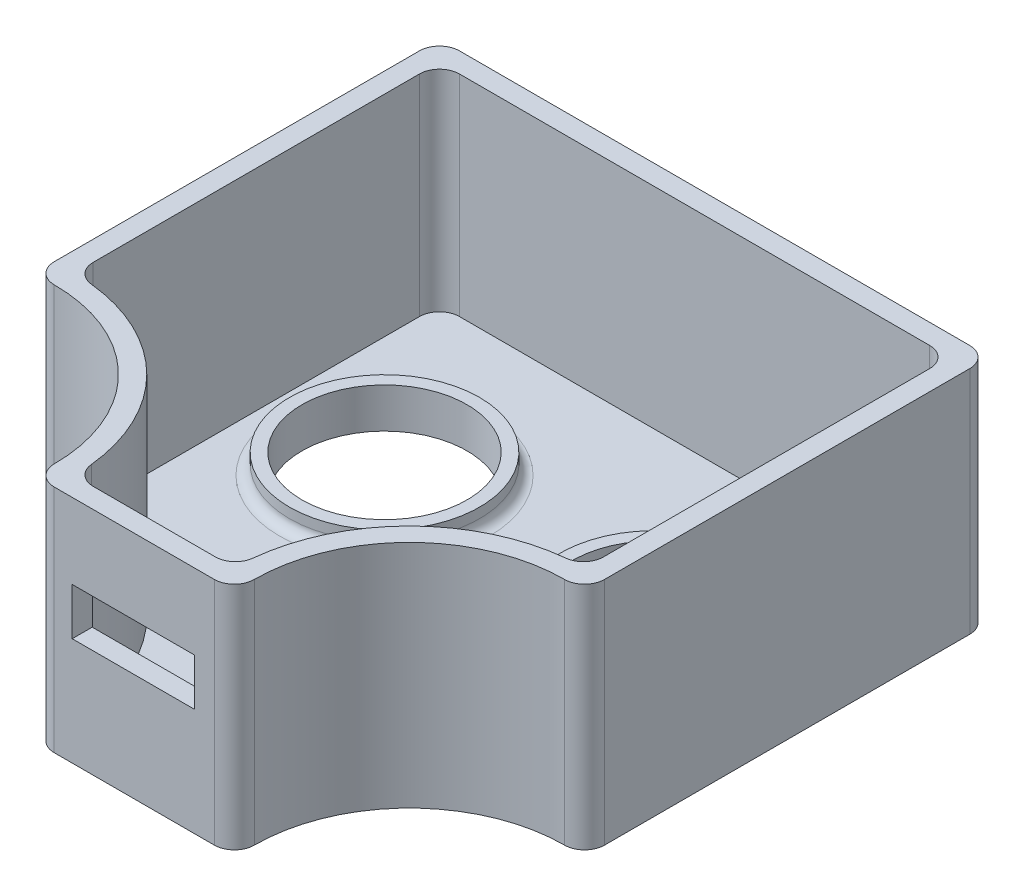
SolidWorks part; units mm, degrees
ref_plane "Alzado" through (0, 0, 0) normal (0, 0, 1) x (1, 0, 0)
ref_plane "Planta" through (0, 0, 0) normal (0, 1, 0) x (1, 0, 0)
ref_plane "Vista lateral" through (0, 0, 0) normal (1, 0, 0) x (0, 0, -1)
sketch "Croquis1" plane through (0, 0, 0) normal (0, 1, 0) x (1, 0, 0)
  line L0 (-13.8608, 0) -> (-3.3608, 0) construction
  line L1 (-8.6108, 17.491) -> (-8.6108, -38.509) construction
  line L2 (-8.7014, -42.647) -> (-14.8014, -42.647) construction
  line L3 (-32.1108, 17.491) -> (14.8892, 17.491)
  line L4 (-34.1108, 15.491) -> (-34.1108, -17.1118)
  line L5 (16.8892, -36.3999) -> (16.8892, -36.509)
  line L6 (16.8892, 15.491) -> (16.8892, -17.1118)
  line L7 (-34.1108, 17.491) -> (16.8892, -36.509) construction
  line L8 (-34.1108, -36.509) -> (16.8892, 17.491) construction
  line L9 (-34.1108, 19.491) -> (16.8892, 19.491)
  line L10 (-36.1108, 17.491) -> (-36.1108, -19.009)
  line L11 (-16.6108, -38.509) -> (-0.6108, -38.509)
  line L12 (18.8892, 17.491) -> (18.8892, -19.009)
  line L13 (-36.1108, 19.491) -> (18.8892, -38.509) construction
  line L14 (-36.1108, -38.509) -> (18.8892, 19.491) construction
  line L15 (-8.7014, -42.647) -> (-2.6014, -42.647)
  line L16 (-14.8014, -42.647) -> (-14.8014, -34.0287) construction
  line L17 (-14.8014, -34.0287) -> (-2.6014, -34.0287) construction
  line L18 (-2.6014, -34.0287) -> (-2.6014, -42.647) construction
  line L20 (-34.1108, -36.3999) -> (-34.1108, -36.509)
  line L21 (-14.7136, -36.509) -> (-2.5079, -36.509)
  circle A0 centre (-22.1108, 0) radius 8.25
  circle A1 centre (4.8892, 0) radius 8.25
  circle A2 centre (-22.1108, 0) radius 9.5
  circle A3 centre (4.8892, 0) radius 9.5
  arc A4 (-16.7031, -34.7141) -> (-32.3159, -19.1013) centre (-34.1108, -36.509) ccw
  arc A5 (-18.6108, -36.509) -> (-34.1108, -21.009) centre (-34.1108, -36.509) ccw
  arc A6 (15.0943, -19.1013) -> (-0.5185, -34.7141) centre (16.8892, -36.509) ccw
  arc A7 (16.8892, -21.009) -> (1.3892, -36.509) centre (16.8892, -36.509) ccw
  arc A8 (-32.3159, -19.1013) -> (-34.1108, -17.1118) centre (-32.1108, -17.1118) cw
  arc A9 (-36.1108, -19.009) -> (-34.1108, -21.009) centre (-34.1108, -19.009) ccw
  arc A10 (-16.7031, -34.7141) -> (-14.7136, -36.509) centre (-14.7136, -34.509) ccw
  arc A11 (-18.6108, -36.509) -> (-16.6108, -38.509) centre (-16.6108, -36.509) ccw
  arc A12 (1.3892, -36.509) -> (-0.6108, -38.509) centre (-0.6108, -36.509) cw
  arc A13 (-2.5079, -36.509) -> (-0.5185, -34.7141) centre (-2.5079, -34.509) ccw
  arc A14 (18.8892, -19.009) -> (16.8892, -21.009) centre (16.8892, -19.009) cw
  arc A15 (16.8892, -17.1118) -> (15.0943, -19.1013) centre (14.8892, -17.1118) cw
  arc A16 (18.8892, 17.491) -> (16.8892, 19.491) centre (16.8892, 17.491) ccw
  arc A17 (-34.1108, 19.491) -> (-36.1108, 17.491) centre (-34.1108, 17.491) ccw
  arc A18 (16.8892, 15.491) -> (14.8892, 17.491) centre (14.8892, 15.491) ccw
  arc A19 (-32.1108, 17.491) -> (-34.1108, 15.491) centre (-32.1108, 15.491) ccw
  point P6 (-8.6108, 0)
  point P9 (-8.6108, -9.509)
  point P16 (-8.6108, -9.509)
  dimension "D1" = 16.5
  dimension "D2" = 16.5
  dimension "D6" = 19
  dimension "D7" = 19
  dimension "D8" = 54
  dimension "D12" = 35
  dimension "D13" = 31
  dimension "D14" = 35
  dimension "D15" = 31
  dimension "D16" = 2
  dimension "D3" = 27
  dimension "D4" = 56
  dimension "D5" = 51
  dimension "D9" = 55
  dimension "D10" = 6.1
  dimension "D11" = 6.1
extrude "Saliente-Extruir1" add sketch "Croquis1" along normal blind 23 contours L9 A17 L10 A9 A5 A11 L11 A12 A7 A14 L12 A16 A19 L3 A18 L6 A15 A6 A13 L21 A10 A4 A8 L4 region at (-8.6108, 0, -18.6917)
extrude "Saliente-Extruir2" add sketch "Croquis1<4>" along normal blind 2 contours L3 A19 L4 A8 A4 A10 L21 A13 A6 A15 L6 A18 A3 A2 region at (-8.6108, 0, 7.1402)
sketch "Croquis1<4>" plane through (0, 0, 0) normal (0, 1, 0) x (1, 0, 0) same geometry as "Croquis1"
extrude "Saliente-Extruir3" add sketch "Croquis1<6>" along normal blind 4 contours A2 A0 | A3 A1 region at (-31.3421, 0, 0) region at (-4.3421, 0, 0)
sketch "Croquis1<6>" plane through (0, 0, 0) normal (0, 1, 0) x (1, 0, 0) same geometry as "Croquis1"
sketch "Croquis2" plane through (0, 0, 38.509) normal (0, 0, 1) x (1, 0, 0)
  line L1 (-14.814, 15.4649) -> (-2.614, 15.4649)
  line L2 (-14.814, 15.4649) -> (-14.814, 10.7649)
  line L3 (-14.814, 10.7649) -> (-2.614, 10.7649)
  line L4 (-2.614, 15.4649) -> (-2.614, 10.7649)
  line L5 (-14.814, 15.4649) -> (-2.614, 10.7649) construction
  line L6 (-14.814, 10.7649) -> (-2.614, 15.4649) construction
  point P0 (-8.714, 13.1149)
  dimension "D1" = 12.2
  dimension "D2" = 4.7
extrude "Cortar-Extruir4" cut sketch "Croquis2" against normal blind 4
fillet "Redondeo1" radius 1 1 edges at (-22.1108, 2, 9.5)
fillet "Redondeo2" radius 1 1 edges at (4.8892, 2, 9.5)
